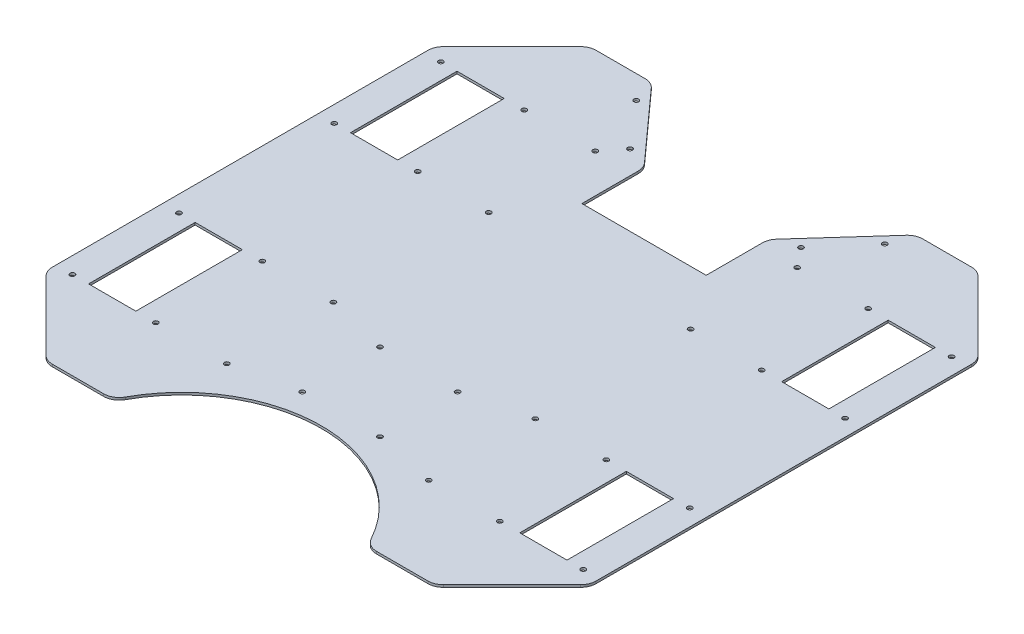
SolidWorks part; units mm, degrees
material "PMMA"
ref_plane "前视基准面" through (0, 0, 0) normal (0, 0, 1) x (1, 0, 0)
ref_plane "上视基准面" through (0, 0, 0) normal (0, 1, 0) x (1, 0, 0)
ref_plane "右视基准面" through (0, 0, 0) normal (1, 0, 0) x (0, 0, -1)
other "Configuration Table"
sketch "草图1" plane through (0, 0, 0) normal (0, 1, 0) x (1, 0, 0)
  line L0 (-125, 175) -> (-175, 125)
  line L1 (125, -175) -> (81.7103, -175)
  line L2 (175, -125) -> (175, 125)
  line L3 (125, 175) -> (85, 175)
  line L4 (-175, -125) -> (-175, 125)
  line L5 (-85, 175) -> (-40, 125)
  line L7 (125, 175) -> (175, 125)
  line L8 (175, -125) -> (125, -175)
  line L9 (-125, -175) -> (-175, -125)
  line L10 (40, 125) -> (85, 175)
  line L11 (-85, 175) -> (-125, 175)
  line L12 (40, 125) -> (40, 85)
  line L13 (40, 85) -> (-40, 85)
  line L14 (-40, 85) -> (-40, 125)
  line L15 (-153.994, 50) -> (-123.594, 50)
  line L16 (-123.594, 50) -> (-123.594, 118.58)
  line L17 (-123.594, 118.58) -> (-153.994, 118.58)
  line L18 (-153.994, 118.58) -> (-153.994, 50)
  line L19 (123.594, 50) -> (153.994, 50)
  line L20 (153.994, 50) -> (153.994, 118.58)
  line L21 (153.994, 118.58) -> (123.594, 118.58)
  line L22 (123.594, 118.58) -> (123.594, 50)
  line L23 (-175, 0) -> (175, 0) construction
  line L24 (-123.594, -118.58) -> (-153.994, -118.58)
  line L25 (-123.594, -50) -> (-123.594, -118.58)
  line L26 (-153.994, -50) -> (-123.594, -50)
  line L27 (-153.994, -118.58) -> (-153.994, -50)
  line L28 (153.994, -118.58) -> (123.594, -118.58)
  line L29 (153.994, -50) -> (153.994, -118.58)
  line L30 (123.594, -50) -> (153.994, -50)
  line L31 (123.594, -118.58) -> (123.594, -50)
  line L32 (-81.7103, -175) -> (-125, -175)
  line L33 (-80, 160) -> (-55, 131) construction
  circle A0 centre (-55, 131) radius 1.55
  circle A1 centre (-80, 160) radius 1.55
  circle A2 centre (55, 131) radius 1.55
  circle A3 centre (80, 160) radius 1.55
  circle A4 centre (-65, 118.58) radius 1.55
  circle A5 centre (-65, 50) radius 1.55
  circle A6 centre (-110.72, 50) radius 1.55
  circle A7 centre (-110.72, 118.58) radius 1.55
  circle A12 centre (-164.434, 118.58) radius 1.55
  circle A13 centre (-164.434, 50) radius 1.55
  circle A14 centre (-65, -118.58) radius 1.55
  circle A15 centre (-65, -50) radius 1.55
  circle A16 centre (-110.72, -50) radius 1.55
  circle A17 centre (-110.72, -118.58) radius 1.55
  circle A18 centre (-164.434, -50) radius 1.55
  circle A19 centre (-164.434, -118.58) radius 1.55
  circle A20 centre (65, 50) radius 1.55
  circle A21 centre (110.72, 50) radius 1.55
  circle A22 centre (110.72, 118.58) radius 1.55
  circle A23 centre (65, 118.58) radius 1.55
  circle A24 centre (164.434, 118.58) radius 1.55
  circle A25 centre (164.434, 50) radius 1.55
  circle A26 centre (164.434, -118.58) radius 1.55
  circle A27 centre (164.434, -50) radius 1.55
  circle A28 centre (110.72, -50) radius 1.55
  circle A29 centre (110.72, -118.58) radius 1.55
  circle A30 centre (65, -118.58) radius 1.55
  circle A31 centre (65, -50) radius 1.55
  arc A32 (-81.7103, -175) -> (81.7103, -175) centre (0, -212.7283) cw
  circle A33 centre (25, -60) radius 1.55
  circle A34 centre (25, -110) radius 1.55
  circle A35 centre (-25, -60) radius 1.55
  circle A36 centre (-25, -110) radius 1.55
  point P0 (0, 0)
  point P1 (-85, 175)
  point P2 (85, 175)
  point P3 (40, 125)
  point P4 (-40, 125)
  point P6 (125, 175)
  point P8 (175, 125)
  point P10 (175, -125)
  point P11 (125, -175)
  point P12 (-125, -175)
  point P13 (-175, -125)
  point P24 (-80, 160)
  point P25 (-55, 131)
  point P26 (55, 131)
  point P27 (80, 160)
  point P36 (-164.434, 118.58)
  point P37 (-164.434, 50)
  point P38 (-153.994, 118.58)
  point P39 (-123.594, 50)
  point P40 (-110.72, 118.58)
  point P41 (-110.72, 50)
  point P42 (-65, 118.58)
  point P43 (-65, 50)
  point P47 (-123.594, 118.58)
  point P53 (-153.994, 50)
  point P66 (-40, 85)
  point P67 (40, 85)
  point P70 (110.72, 50)
  point P71 (65, 50)
  point P72 (123.594, 50)
  point P73 (153.994, 50)
  point P74 (164.434, 50)
  point P75 (65, 118.58)
  point P76 (110.72, 118.58)
  point P77 (123.594, 118.58)
  point P78 (153.994, 118.58)
  point P81 (164.434, 118.58)
  point P85 (-65, -118.58)
  point P88 (-65, -50)
  point P91 (-110.72, -50)
  point P94 (-110.72, -118.58)
  point P101 (-164.434, -50)
  point P104 (-164.434, -118.58)
  point P118 (164.434, -118.58)
  point P121 (164.434, -50)
  point P128 (110.72, -50)
  point P131 (110.72, -118.58)
  point P134 (65, -118.58)
  point P137 (65, -50)
  dimension "D29" = 3.1
  dimension "D30" = 3.1
  dimension "D31" = 3.1
  dimension "D32" = 3.1
  dimension "D40" = 3.1
  dimension "D41" = 3.1
  dimension "D42" = 3.1
  dimension "D43" = 3.1
  dimension "D44" = 3.1
  dimension "D45" = 3.1
  dimension "D46" = 3.1
  dimension "D47" = 3.1
  dimension "D48" = 3.1
  dimension "D49" = 3.1
  dimension "D60" = 3.1
  dimension "D61" = 3.1
  dimension "D62" = 43.2897
  dimension "D63" = 90
  dimension "D67" = 3.1
  dimension "D68" = 3.1
  dimension "D69" = 3.1
  dimension "D70" = 3.1
  dimension "D1" = 175
  dimension "D2" = 175
  dimension "D3" = 125
  dimension "D4" = 125
  dimension "D5" = 125
  dimension "D6" = 125
  dimension "D7" = 125
  dimension "D8" = 125
  dimension "D9" = 125
  dimension "D10" = 125
  dimension "D11" = 175
  dimension "D12" = 175
  dimension "D13" = 40
  dimension "D14" = 40
  dimension "D15" = 85
  dimension "D16" = 85
  dimension "D17" = 125
  dimension "D18" = 125
  dimension "D19" = 40
  dimension "D20" = 45
  dimension "D21" = 160
  dimension "D22" = 160
  dimension "D23" = 80
  dimension "D24" = 80
  dimension "D25" = 55
  dimension "D26" = 131
  dimension "D27" = 55
  dimension "D28" = 131
  dimension "D33" = 50
  dimension "D34" = 118.58
  dimension "D35" = 65
  dimension "D36" = 45.72
  dimension "D37" = 12.874
  dimension "D38" = 30.4
  dimension "D39" = 10.44
  dimension "D50" = 40
  dimension "D51" = 40
  dimension "D52" = 85
  dimension "D53" = 85
  dimension "D54" = 138.013
  dimension "D55" = 65
  dimension "D56" = 45.72
  dimension "D57" = 12.874
  dimension "D58" = 30.4
  dimension "D59" = 10.44
  dimension "D64" = 0
  dimension "D65" = 25
  dimension "D66" = 25
  dimension "D71" = 60
  dimension "D72" = 50
extrude "凸台-拉伸1" add sketch "草图1" along normal blind 1.5 contours A1 | A0 | L8 L1 A32 L32 L9 L4 L0 L11 L5 L14 L13 L12 L10 L3 L7 L2 | A5 | A3 | A2 | A4 | A7 | A12 | L16 L17 L18 L15 | A6 | L21 L22 L19 L20 | A13 | A16 | A17 | A14 | A15 | A18 | A19 | L25 L24 L27 L26 | A20 | A21 | A22 | A23 | A24 | A25 | A28 | A26 | A27 | L28 L31 L30 L29 | A30 | A31 | A29 | A35 | A36 | A33 | A34
fillet "圆角1" radius 10 1 edges at (-40, 0.75, -125)
fillet "圆角2" radius 10 1 edges at (40, 0.75, -125)
fillet "圆角3" radius 10 12 edges at (-85, 0.75, -175) (85, 0.75, -175) (125, 0.75, -175) (175, 0.75, -125) (175, 0.75, 125) (125, 0.75, 175) (81.7103, 0.75, 175) (-81.7103, 0.75, 175) (-125, 0.75, 175) (-175, 0.75, 125) (-175, 0.75, -125) (-125, 0.75, -175)
